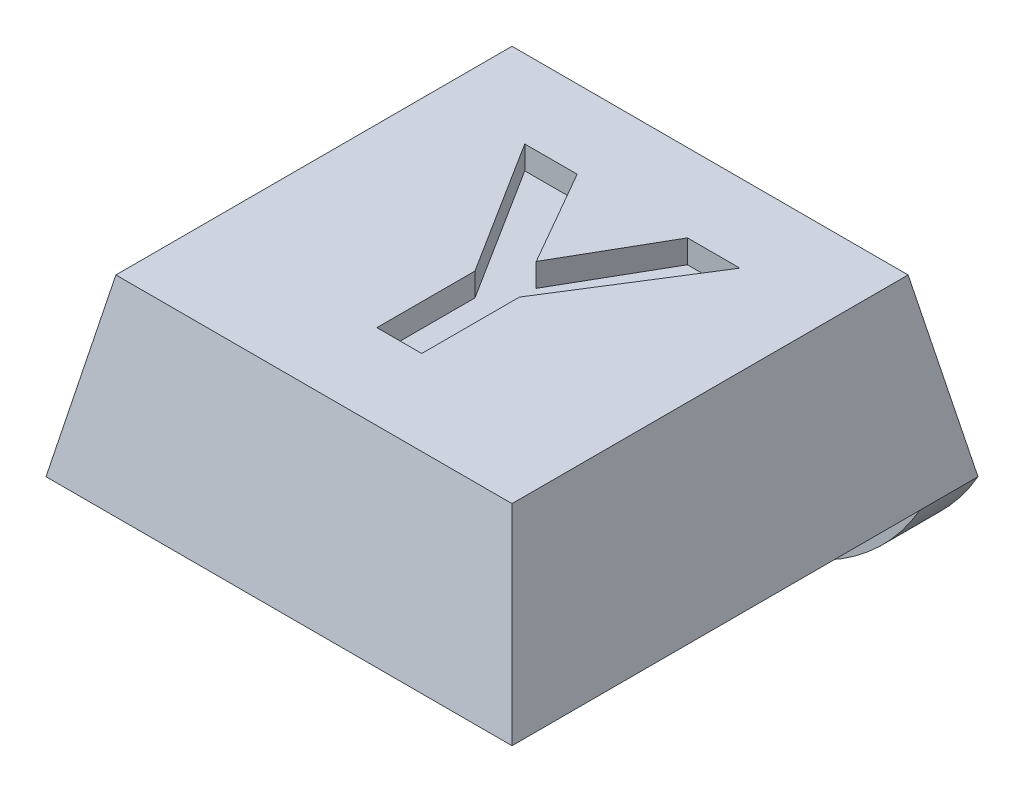
SolidWorks part; units mm, degrees
ref_plane "Front Plane" through (0, 0, 0) normal (0, 0, 1) x (1, 0, 0)
ref_plane "Top Plane" through (0, 0, 0) normal (0, 1, 0) x (1, 0, 0)
ref_plane "Right Plane" through (0, 0, 0) normal (1, 0, 0) x (0, 0, -1)
sketch "Sketch1" plane through (0, 0, 0) normal (0, 1, 0) x (1, 0, 0)
  line L1 (0, 0) -> (8, 0)
  line L2 (0, 0) -> (0, 8)
  line L3 (0, 8) -> (8, 8)
  line L4 (8, 0) -> (8, 8)
  dimension "D1" = 8
  dimension "D2" = 8
extrude "Boss-Extrude1" add sketch "Sketch1" along normal blind 3
sketch "Sketch2" plane through (0, 0, 0) normal (0, 0, 1) x (1, 0, 0)
  line L0 (0, 0) -> (0.6, 3)
  line L1 (0, 3) -> (8, 3) construction
  line L2 (0.6, 3) -> (0, 3)
  line L3 (0, 3) -> (0, 0)
  line L4 (8, 0) -> (7.4, 3)
  line L5 (7.4, 3) -> (8, 3)
  line L6 (8, 3) -> (8, 0)
  dimension "D1" = 0.6
  dimension "D2" = 0.6
extrude "Cut-Extrude1" cut sketch "Sketch2" against normal through all both and the other way through all
sketch "Sketch3" plane through (0, 0, 0) normal (1, 0, 0) x (0, 0, -1)
  line L0 (0, 0) -> (0.6, 3)
  line L1 (8, 3) -> (0, 3) construction
  line L2 (0.6, 3) -> (0, 3)
  line L3 (0, 3) -> (0, 0)
  line L4 (8, 3) -> (7.4, 3)
  line L5 (7.4, 3) -> (8, 0)
  line L6 (8, 3) -> (8, 0)
  dimension "D1" = 0.6
  dimension "D2" = 0.6
extrude "Cut-Extrude2" cut sketch "Sketch3" along normal blind 11
sketch "Sketch4" plane through (0, 0, 0) normal (0, -1, 0) x (1, 0, 0)
  line L0 (8, 0) -> (8, -8) construction
  line L3 (0, 0) -> (8, 0) construction
  circle A0 centre (4, -3.75) radius 1.8
  dimension "D1" = 3.6
  dimension "D2" = 4
  dimension "D3" = 3.75
extrude "Cut-Extrude3" cut sketch "Sketch4" against normal blind 0.8
sketch "Sketch5" plane through (0, 0, 0) normal (0, -1, 0) x (1, 0, 0)
  line L0 (8, 0) -> (8, -8) construction
  line L1 (0, -8) -> (8, -8)
  line L2 (0, -8) -> (0, -7)
  line L3 (0, -7) -> (8, -7)
  line L4 (8, -8) -> (8, -7)
  dimension "D1" = 1
extrude "Boss-Extrude2" add sketch "Sketch5" along normal blind 2
fillet "Fillet1" radius 4 2 edges at (8, -2, -7.5) (0, -2, -7.5)
sketch "Sketch6" plane through (0, 3, 0) normal (0, 1, 0) x (1, 0, 0)
  text T0 "Y" font "Arial" height 4
extrude "Cut-Extrude4" cut sketch "Sketch6" against normal blind 0.4
